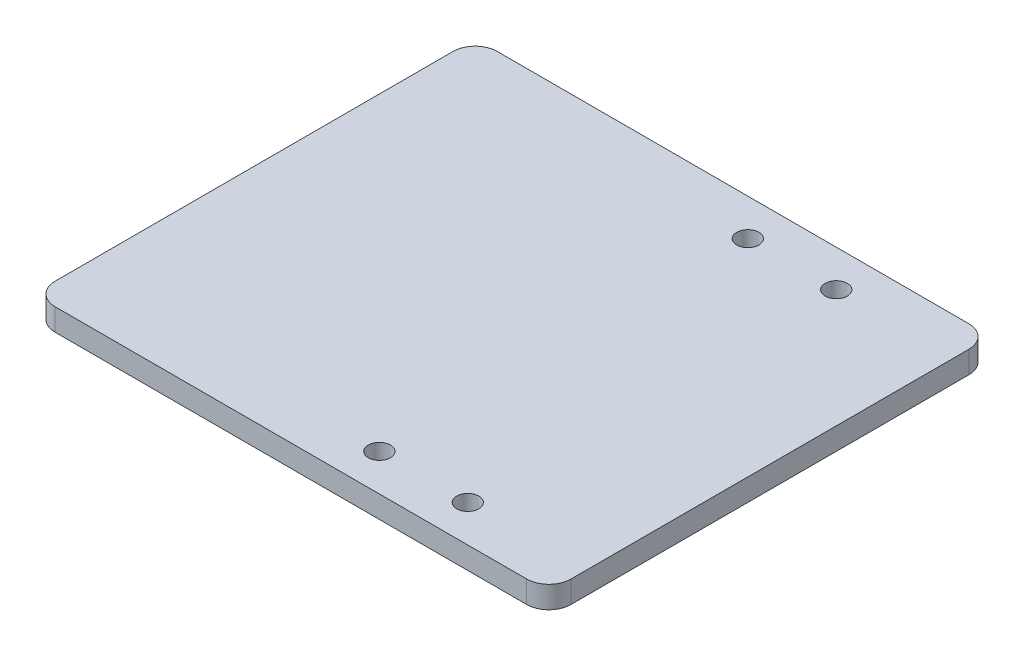
SolidWorks part; units mm, degrees
ref_plane "前视基准面" through (0, 0, 0) normal (0, 0, 1) x (1, 0, 0)
ref_plane "上视基准面" through (0, 0, 0) normal (0, 1, 0) x (1, 0, 0)
ref_plane "右视基准面" through (0, 0, 0) normal (1, 0, 0) x (0, 0, -1)
sketch "草图1" plane through (0, 0, 0) normal (0, 1, 0) x (1, 0, 0)
  line L1 (0, 0) -> (70, 0)
  line L2 (0, 0) -> (0, -60)
  line L3 (0, -60) -> (70, -60)
  line L4 (70, 0) -> (70, -60)
  dimension "D1" = 60
  dimension "D2" = 70
extrude "凸台-拉伸1" add sketch "草图1" along normal blind 3
sketch "草图2" plane through (0, 3, 0) normal (0, 1, 0) x (1, 0, 0)
  circle A0 centre (54, -5) radius 1.5
  circle A1 centre (42, -5) radius 1.5
  circle A2 centre (54, -55) radius 1.5
  circle A3 centre (42, -55) radius 1.5
  dimension "D1" = 3
extrude "切除-拉伸1" cut sketch "草图2" against normal through all
fillet "圆角1" radius 3 4 edges at (0, 1.5, 60) (0, 1.5, 0) (70, 1.5, 0) (70, 1.5, 60)
